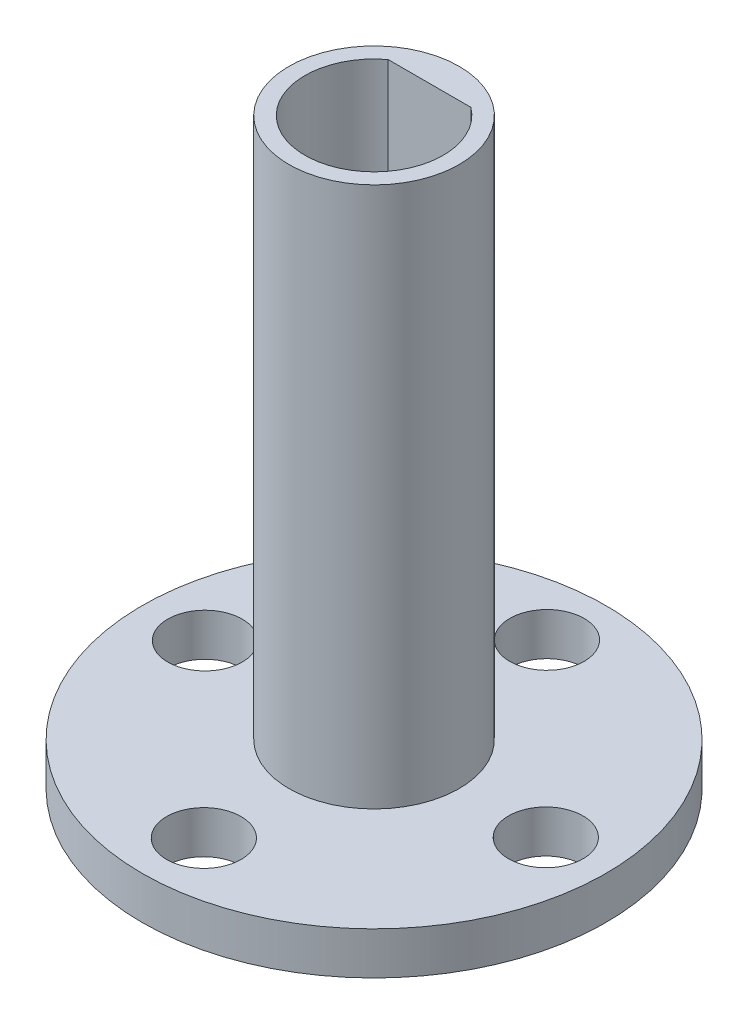
SolidWorks part; units mm, degrees
ref_plane "Front Plane" through (0, 0, 0) normal (0, 0, 1) x (1, 0, 0)
ref_plane "Top Plane" through (0, 0, 0) normal (0, 1, 0) x (1, 0, 0)
ref_plane "Right Plane" through (0, 0, 0) normal (1, 0, 0) x (0, 0, -1)
sketch "Sketch3" plane through (0, 0, 0) normal (0, 1, 0) x (1, 0, 0)
  line L0 (-7.9995, 0.0532) -> (0.009, 8.1156) construction
  line L1 (0.009, 8.1156) -> (8.0177, 0.0533) construction
  line L2 (8.0177, 0.0533) -> (0.0092, -8.0091) construction
  line L3 (0.0092, -8.0091) -> (-7.9995, 0.0532) construction
  line L5 (0.009, -3.25) -> (0.009, 2.6055)
  line L7 (18.7783, 0.0532) -> (-25.5315, 0.0532) construction
  line L8 (9.7482, 0.0532) -> (10.8982, 0.0532)
  line L9 (-1.9426, 2.6055) -> (1.9426, 2.6055)
  line L11 (0.009, -13.1564) -> (0.009, 16.0208) construction
  circle A0 centre (0, 0) radius 10.9
  circle A1 centre (0.009, 8.1156) radius 1.75
  circle A2 centre (8.0177, 0.0533) radius 1.75
  circle A3 centre (0.0092, -8.0091) radius 1.75
  circle A4 centre (-7.9995, 0.0532) radius 1.75
  circle A5 centre (0, 0) radius 4
  arc A6 (-1.9426, 2.6055) -> (1.9426, 2.6055) centre (0, 0) ccw
  point P13 (0, 0)
  dimension "D1" = 21.8
extrude "Boss-Extrude1" add sketch "Sketch3" along normal blind 27.4 contours A5 | A6 L9
extrude "Boss-Extrude2" add sketch "Sketch3<17>" along normal blind 2 contours A4 | A3 | A2 | A1 | A0
sketch "Sketch3<17>" plane through (0, 0, 0) normal (0, 1, 0) x (1, 0, 0) same geometry as "Sketch3"
